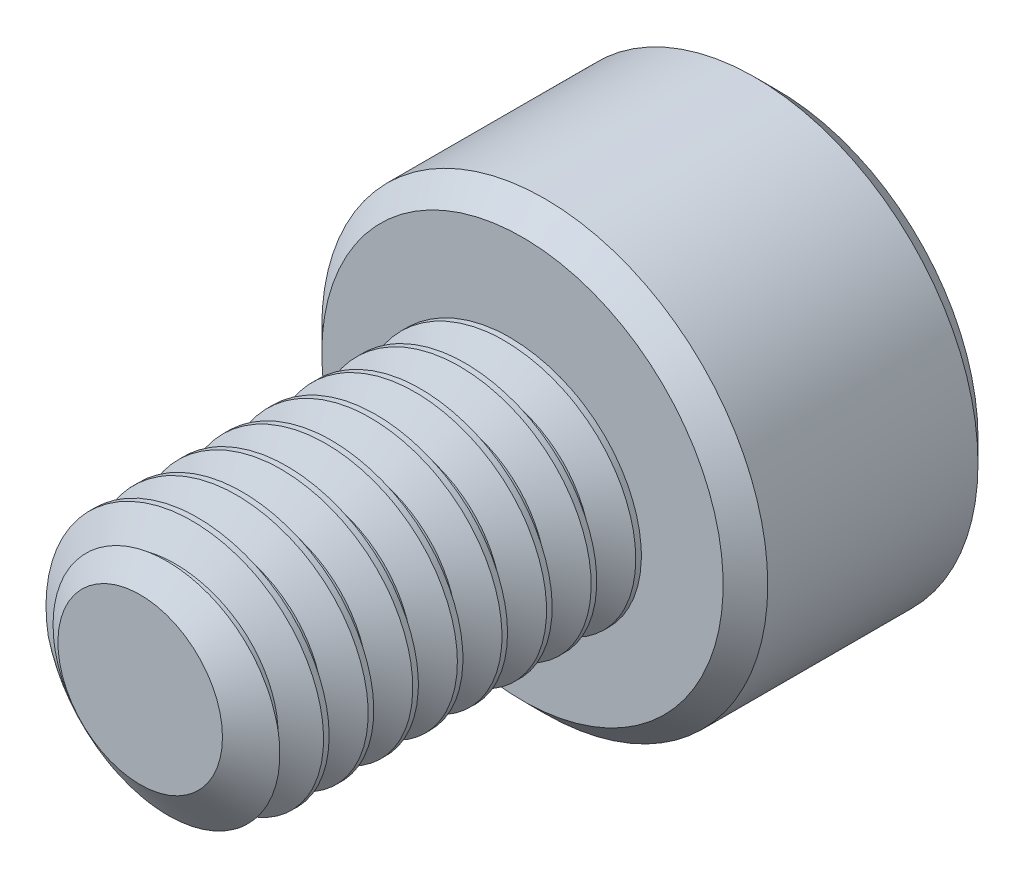
SolidWorks part; units mm, degrees
other "DetailItem1"
ref_plane "Front Plane" through (0, 0, 0) normal (0, 0, 1) x (1, 0, 0)
ref_plane "Top Plane" through (0, 0, 0) normal (0, 1, 0) x (1, 0, 0)
ref_plane "Right Plane" through (0, 0, 0) normal (1, 0, 0) x (0, 0, -1)
sketch "Sketch1" plane through (0, 0, 0) normal (0, 0, 1) x (1, 0, 0)
  circle A0 centre (0, 0) radius 2
  dimension "OD" = 4
extrude "Extrude1" add sketch "Sketch1" against normal blind 6
sketch "Sketch2" plane through (0, 0, 0) normal (0, 0, 1) x (1, 0, 0)
  circle A0 centre (0, 0) radius 2 construction
  circle A1 centre (0, 0) radius 2
curve "Helix/Spiral1" pitch 0.7 height 6.7 radius 2 centre (0, 0, 0) axis (0, 0, -1) start towards (0, 1, 0) parameters "pitch"=0.7
sketch "Sketch3" plane through (0, 0, 0) normal (1, 0, 0) x (0, 0, -1)
  line L0 (-0.6125, 2) -> (-0.35, 1.5453)
  line L1 (-0.35, 1.5453) -> (-0.2625, 1.5453)
  line L2 (-0.2625, 1.5453) -> (0, 2)
  line L3 (-0.6125, 2) -> (0, 2)
  line L4 (-0.3062, 2) -> (-0.3062, 1.5453) construction
  line L5 (-0.4812, 1.7727) -> (-0.1312, 1.7727) construction
  line L6 (0, 2) -> (0, -2) construction
  dimension "D1" = 0.0875
  dimension "D2" = 0.35
  dimension "D3" = 60
sweep "Cut-Sweep1" cut profiles "Sketch3" path "Helix/Spiral1" align with end faces yes
sketch "Sketch4" plane through (0, 0, 0) normal (1, 0, 0) x (0, 0, -1)
  line L0 (0.4962, 2) -> (0, 1.2913)
  line L1 (0, 1.2913) -> (0, 2)
  line L2 (0.4962, 2) -> (0, 2)
  line L3 (-0.6125, 2) -> (0, 2) construction
  line L4 (0, 0) -> (7.0209, 0) construction
  dimension "D1" = 55
  dimension "D2" = 0.254
revolve "Cut-Revolve1" cut sketch "Sketch4" angle 360 about L4
sketch "Sketch6" plane through (0, 0, -6) normal (0, 0, -1) x (-1, 0, 0)
  circle A0 centre (0, 0) radius 3.5
  dimension "head dia" = 7
extrude "Extrude2" add sketch "Sketch6" along normal blind 4
sketch "Sketch7" plane through (0, 0, -10) normal (0, 0, -1) x (-1, 0, 0)
  line L1 (0, 1.7321) -> (-1.5, 0.866)
  line L2 (-1.5, 0.866) -> (-1.5, -0.866)
  line L3 (-1.5, -0.866) -> (0, -1.7321)
  line L4 (0, -1.7321) -> (1.5, -0.866)
  line L5 (1.5, -0.866) -> (1.5, 0.866)
  line L6 (1.5, 0.866) -> (0, 1.7321)
  circle A0 centre (0, 0) radius 1.5 construction
  dimension "hex dia" = 3
extrude "Cut-Extrude1" cut sketch "Sketch7" against normal blind 2.25
sketch "Sketch8" plane through (0, 0, -10) normal (0, 0, -1) x (-1, 0, 0)
  circle A0 centre (0, 0) radius 1.7321
extrude "Cut-Extrude2" cut sketch "Sketch8" against normal through all draft 45
chamfer "Chamfer1" distance 0.35 angle 45 2 edges at (-3.5, 0, -10) (-3.5, 0, -6)
sketch "Sketch10" plane through (0, 0, -6) normal (0, 0, 1) x (1, 0, 0)
  circle A1 centre (0, 0) radius 2
  circle A2 centre (0, 0) radius 2
  dimension "D1" = 0
ref_plane "Plane1" through (0, 0, 0) normal (0, 0, 1) x (1, 0, 0)
extrude "partial thread" [suppressed] add sketch "Sketch10" along normal up to surface (10 mm away) separate body up to plane "Plane1"
chamfer "Chamfer2" [suppressed] distance 0.08 angle 45
combine bodies "Combine1" [suppressed] operation type add bodies to combine 107 108
sketch "Sketch9" plane through (0, 0, 0) normal (1, 0, 0) x (0, 0, -1)
  line L0 (0, 2) -> (0, -2) construction
  line L1 (1.75, 2) -> (1.75, -2) construction
  dimension "D1" = 1.75
equation "\"D3@Helix/Spiral1\" = \"screw length@Extrude1\"+\"pitch@Helix/Spiral1\""
equation "\"D1@Sketch3\" = \"pitch@Helix/Spiral1\"*.125"
equation "\"D2@Sketch3\" = \"pitch@Helix/Spiral1\"*.5"
equation "\"D1@Cut-Extrude1\" = \"hex dia@Sketch7\"*.75"
equation "\"D1@Chamfer1\" = \"head dia@Sketch6\"*.05"
equation "\"D1@Sketch9\" = \"pitch@Helix/Spiral1\"*2.5"
equation "\"D1@Chamfer2\"=\"OD@Sketch1\"*.02"
